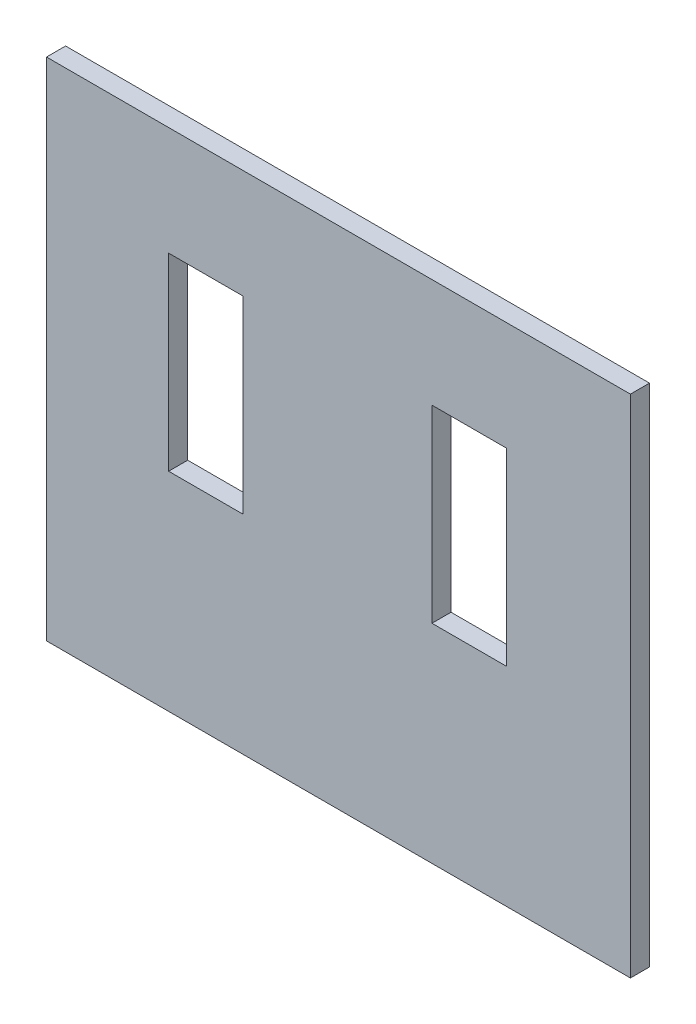
SolidWorks part; units mm, degrees
ref_plane "Plano frontal" through (0, 0, 0) normal (0, 0, 1) x (1, 0, 0)
ref_plane "Plano superior" through (0, 0, 0) normal (0, 1, 0) x (1, 0, 0)
ref_plane "Plano direito" through (0, 0, 0) normal (1, 0, 0) x (0, 0, -1)
sketch "Esboço6" plane through (0, 0, 0) normal (0, 0, 1) x (1, 0, 0)
  line L1 (0, 0) -> (3060, 0)
  line L2 (0, 0) -> (0, 2650)
  line L3 (0, 2650) -> (3060, 2650)
  line L4 (3060, 0) -> (3060, 2650)
extrude "Ressalto-extrusão2" add sketch "Esboço6" along normal blind 100
sketch "Esboço7" plane through (0, 0, 100) normal (0, 0, 1) x (1, 0, 0)
  line L2 (2020, 2080) -> (2020, 1090)
  line L3 (640, 2080) -> (640, 1090)
  line L4 (640, 2080) -> (1030, 2080)
  line L5 (1030, 2080) -> (1030, 1090)
  line L6 (1030, 1090) -> (640, 1090)
  line L7 (2020, 1090) -> (2410, 1090)
  line L8 (2410, 1090) -> (2410, 2080)
  line L9 (2410, 2080) -> (2020, 2080)
extrude "Corte-extrusão1" cut sketch "Esboço7" against normal blind 749
